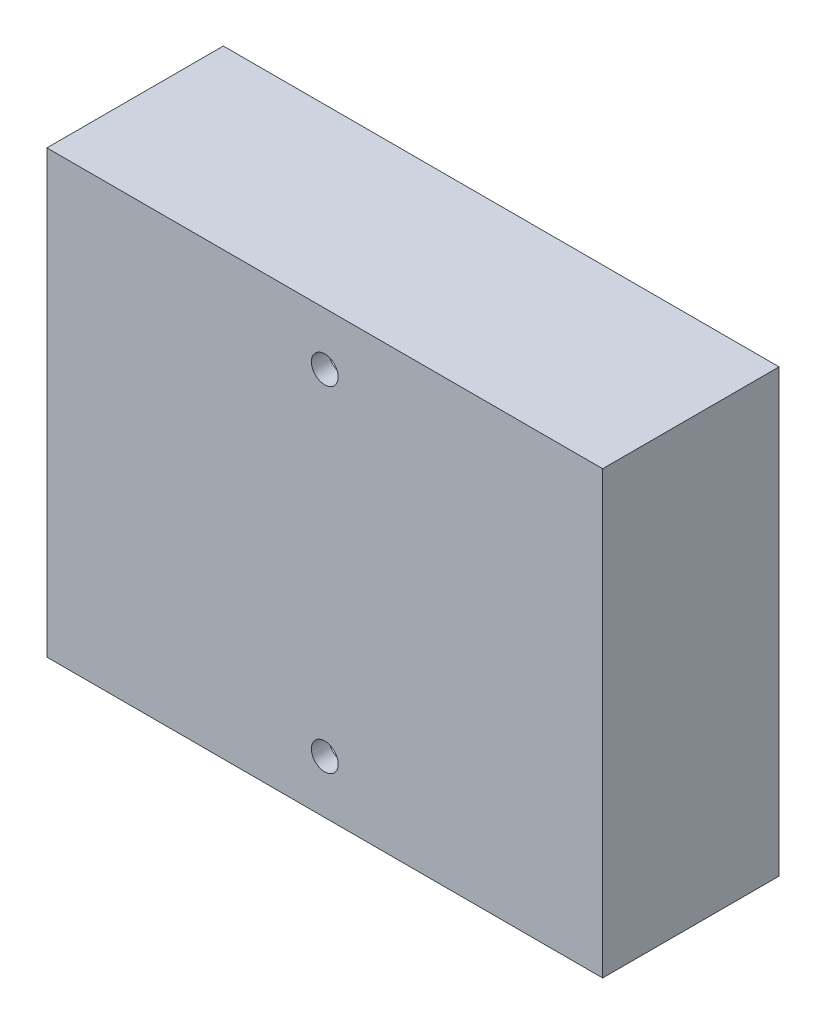
SolidWorks part; units mm, degrees
ref_plane "Front Plane" through (0, 0, 0) normal (0, 0, 1) x (1, 0, 0)
ref_plane "Top Plane" through (0, 0, 0) normal (0, 1, 0) x (1, 0, 0)
ref_plane "Right Plane" through (0, 0, 0) normal (1, 0, 0) x (0, 0, -1)
sketch "Sketch1" plane through (0, 0, 0) normal (0, 0, 1) x (1, 0, 0)
  line L1 (-40.005, 31.75) -> (40.005, 31.75)
  line L2 (-40.005, 31.75) -> (-40.005, -31.75)
  line L3 (-40.005, -31.75) -> (40.005, -31.75)
  line L4 (40.005, 31.75) -> (40.005, -31.75)
  dimension "D1" = 63.5
  dimension "D2" = 80.01
  dimension "D3" = 31.75
  dimension "D4" = 40.005
extrude "Boss-Extrude1" add sketch "Sketch1" along normal blind 25.4
sketch "Sketch2" plane through (0, 0, 0) normal (0, 0, 1) x (1, 0, 0)
  line L1 (31.877, 28.575) -> (-31.877, 28.575)
  line L2 (31.877, 28.575) -> (31.877, -28.575)
  line L3 (31.877, -28.575) -> (-31.877, -28.575)
  line L4 (-31.877, 28.575) -> (-31.877, -28.575)
  line L5 (40.005, -31.75) -> (40.005, 31.75) construction
  line L6 (-40.005, 31.75) -> (-40.005, -31.75) construction
  dimension "D1" = 8.128
  dimension "D2" = 28.575
  dimension "D3" = 57.15
  dimension "D4" = 8.128
extrude "Cut-Extrude1" cut sketch "Sketch2" along normal blind 22.86
sketch "Sketch3" plane through (0, 0, 0) normal (0, 1, 0) x (1, 0, 0)
  line L5 (-40.005, -25.4) -> (-40.005, 0) construction
  line L6 (40.005, -25.4) -> (40.005, 0) construction
  line L7 (-40.005, -12.7) -> (40.005, -12.7) construction
  line L8 (31.877, -5.08) -> (31.877, 0)
  line L9 (-31.877, 0) -> (31.877, 0)
  line L10 (-31.877, -5.08) -> (-31.877, 0)
  line L11 (-31.877, -5.08) -> (31.877, -5.08)
  line L12 (-34.925, 0) -> (34.925, 0) construction
  dimension "D1" = 5.08
  dimension "D2" = 8.128
  dimension "D3" = 8.128
sketch "Sketch6" plane through (0, 0, 0) normal (0, 0, 1) x (1, 0, 0)
  line L0 (0, 31.75) -> (0, -31.75) construction
  line L1 (40.005, 31.75) -> (-40.005, 31.75) construction
  line L2 (-40.005, -31.75) -> (40.005, -31.75) construction
  line L3 (13.97, 0) -> (-13.97, 0) construction
  line L4 (0, -13.97) -> (0, 13.97) construction
  point P6 (0, 24.13)
  point P10 (0, -24.13)
  point P14 (0, -24.13)
  point P15 (0, 24.13)
  dimension "D1" = 7.62
hole_wizard "#8 Clearance Hole1" positions "Sketch7" profile "Sketch8" hole size "#8" standard "ANSI Inch" end condition through all
sketch "Sketch7" plane through (0, 0, 0) normal (0, 0, -1) x (-1, 0, 0)
  point P0 (0, 24.13)
  point P3 (0, -24.13)
  point P6 (0, -24.13)
  point P9 (0, 24.13)
sketch "Sketch8" plane through (0, 24.13, 0) normal (1, 0, 0) x (0, 1, 0)
  line L0 (0, 0) -> (0, 25.4)
  line L1 (0, 25.4) -> (1.9304, 25.4)
  line L2 (1.9304, 25.4) -> (1.9304, 0)
  line L5 (1.9304, 0) -> (0, 0)
  line L11 (0, -6.35) -> (0, 107.95) construction
  dimension "Thru Hole Dia." = 3.8608
  dimension "Thru Hole Depth" = 25.4
sketch "Sketch11" plane through (0, 0, 0) normal (0, 0, 1) x (1, 0, 0)
  line L0 (0, -13.97) -> (0, 13.97) construction
  line L1 (-40.005, -31.75) -> (40.005, -31.75) construction
  point P0 (0, -21.59)
  dimension "D1" = 10.16
sketch "Sketch13" plane through (0, 0, 0) normal (0, 1, 0) x (1, 0, 0)
  line L1 (0, -13.97) -> (0, 13.97) construction
  line L2 (-10.16, 0) -> (-10.16, -21.59)
  line L3 (-10.16, -21.59) -> (10.16, -21.59)
  line L4 (10.16, -21.59) -> (10.16, 0)
  line L6 (-10.16, 0) -> (10.16, 0)
  line L10 (-31.877, 0) -> (31.877, 0) construction
  point P0 (0, 0)
  point P1 (-10.16, -21.59)
  point P2 (0, 0)
  point P4 (10.16, -21.59)
  point P13 (0, 0)
  point P14 (-10.16, -5.08)
  point P15 (0, 0)
  point P16 (0, 0)
  dimension "D1" = 21.59
  dimension "D3" = 10.16
  dimension "D4" = 10.16
extrude "Cut-Extrude3" cut sketch "Sketch13" against normal blind 50.8
